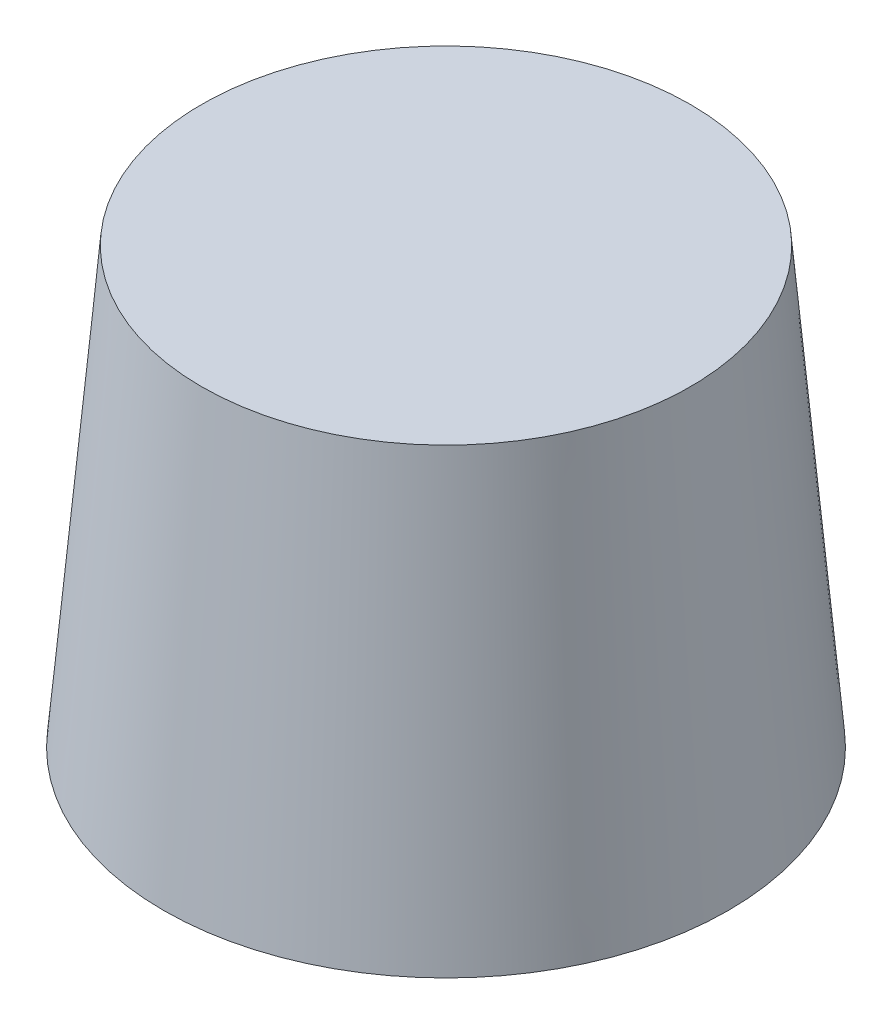
SolidWorks part; units mm, degrees
ref_plane "Front Plane" through (0, 0, 0) normal (0, 0, 1) x (1, 0, 0)
ref_plane "Top Plane" through (0, 0, 0) normal (0, 1, 0) x (1, 0, 0)
ref_plane "Right Plane" through (0, 0, 0) normal (1, 0, 0) x (0, 0, -1)
sketch "Sketch1" plane through (0, 0, 0) normal (0, 1, 0) x (1, 0, 0)
  circle A0 centre (0, 0) radius 8.255
  dimension "top_diameter" = 16.51
extrude "cone" add sketch "Sketch1" along normal blind 12.7 draft 5
